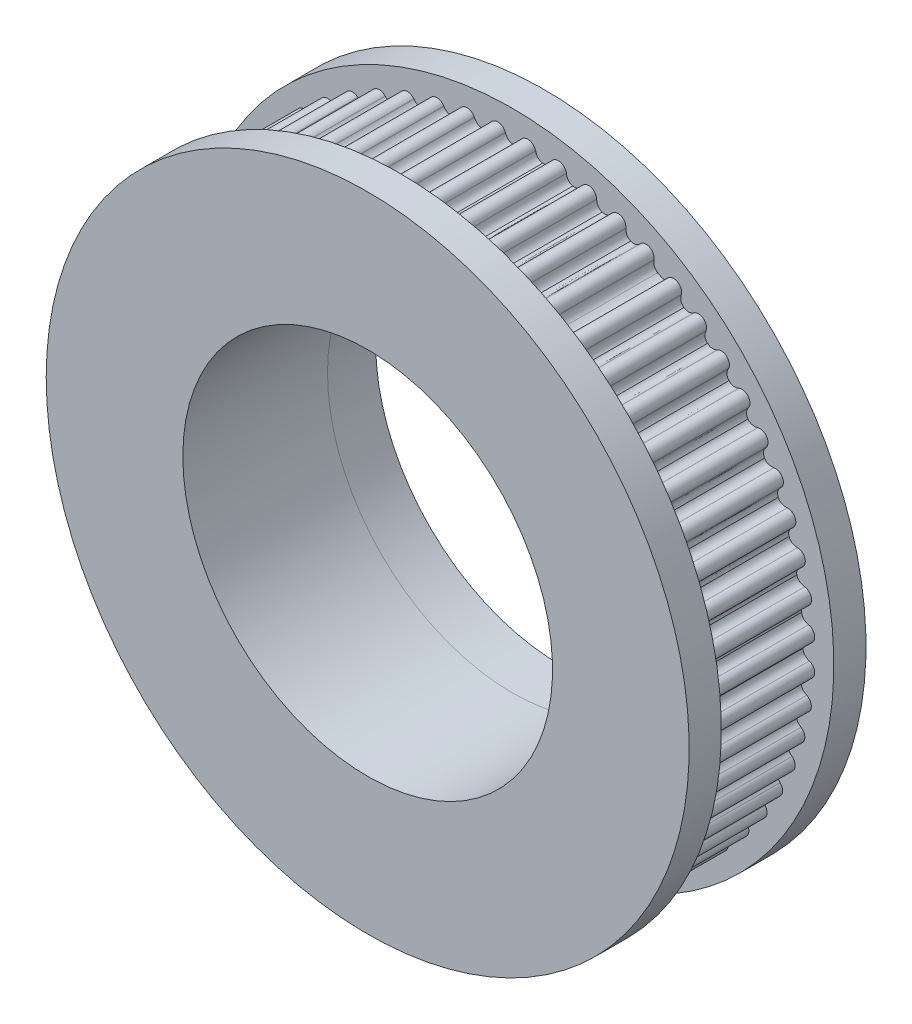
SolidWorks part; units mm, degrees
other "Camera1"
other "Camera2"
other "Camera3"
ref_plane "Front" through (0, 0, 0) normal (0, 0, 1) x (1, 0, 0)
ref_plane "Top" through (0, 0, 0) normal (0, 1, 0) x (1, 0, 0)
ref_plane "Right" through (0, 0, 0) normal (1, 0, 0) x (0, 0, -1)
sketch "Sketch1" plane through (0, 0, 0) normal (1, 0, 0) x (0, 0, -1)
  line L0 (0, 0) -> (-24.4032, 0) construction
  line L1 (0, 11.5) -> (0, 13.5)
  line L2 (0, 13.5) -> (-1, 13.5)
  line L3 (-1, 13.5) -> (-1, 18.85)
  line L4 (-3, 18.85) -> (-10, 18.85)
  line L5 (-12, 18.85) -> (-12, 11.5)
  line L6 (-12, 11.5) -> (0, 11.5)
  line L7 (-1, 18.85) -> (-1, 20)
  line L9 (-3, 20) -> (-3, 18.85)
  line L10 (-12, 13.3586) -> (-1, 13.3586) construction
  line L11 (-6.5, 18.85) -> (-6.5, 22.0506) construction
  line L12 (-10, 20) -> (-10, 18.85)
  line L14 (-12, 18.85) -> (-12, 20)
  line L15 (-12, 18.85) -> (-10, 18.85) construction
  line L16 (-3, 18.85) -> (-1, 18.85) construction
  line L17 (-12, 20) -> (-10, 20)
  line L18 (-3, 20) -> (-1, 20)
  circle A0 centre (-0.5, 11.5) radius 2 construction
  point P22 (-0.5, 13.5)
  point P24 (-6.5, 13.3586)
  dimension "D9" = 4
  dimension "D1" = 12
  dimension "D2" = 11
  dimension "D3" = 7
  dimension "D4" = 37.7
  dimension "D5" = 40
  dimension "D6" = 0
  dimension "D7" = 27
  dimension "D8" = 23
revolve "Revolve1" add sketch "Sketch1" angle 360 about L0
ref_plane "Plane2" through (0, 0, 3) normal (0, 0, 1) x (1, 0, 0)
ref_plane "Plane3" through (0, 0, 10) normal (0, 0, -1) x (-1, 0, 0)
sketch "Sketch3" plane through (0, 0, 3) normal (0, 0, 1) x (1, 0, 0)
  line L0 (0.4895, 18.4804) -> (0.4858, 18.4697)
  line L1 (-0.4323, 18.471) -> (-0.436, 18.4817)
  line L2 (-1.3914, 18.4344) -> (-1.394, 18.4234)
  line L3 (-2.3607, 18.3247) -> (-2.3654, 18.3349)
  line L4 (-3.3107, 18.188) -> (-3.3122, 18.1768)
  line L5 (-4.2632, 17.9775) -> (-4.269, 17.9872)
  line L6 (-5.1937, 17.7423) -> (-5.194, 17.731)
  line L7 (-6.119, 17.4334) -> (-6.1258, 17.4424)
  line L8 (-7.0199, 17.1022) -> (-7.019, 17.0909)
  line L9 (-7.9078, 16.6983) -> (-7.9155, 16.7066)
  line L10 (-8.7691, 16.2747) -> (-8.767, 16.2636)
  line L11 (-9.6099, 15.7803) -> (-9.6184, 15.7877)
  line L12 (-10.4222, 15.269) -> (-10.419, 15.2581)
  line L13 (-11.2067, 14.6893) -> (-11.216, 14.6958)
  line L14 (-11.9612, 14.0959) -> (-11.9568, 14.0855)
  line L15 (-12.6808, 13.4374) -> (-12.6907, 13.4429)
  line L16 (-13.3691, 12.7684) -> (-13.3637, 12.7585)
  line L17 (-14.0159, 12.0383) -> (-14.0263, 12.0427)
  line L18 (-14.6305, 11.301) -> (-14.6241, 11.2917)
  line L19 (-15.1975, 10.5073) -> (-15.2083, 10.5106)
  line L20 (-15.7316, 9.7098) -> (-15.7243, 9.7012)
  line L21 (-16.2125, 8.8612) -> (-16.2236, 8.8633)
  line L22 (-16.6604, 8.0122) -> (-16.6522, 8.0044)
  line L23 (-17.05, 7.118) -> (-17.0612, 7.1189)
  line L24 (-17.4066, 6.2268) -> (-17.3977, 6.22)
  line L25 (-17.7006, 5.2968) -> (-17.7119, 5.2965)
  line L26 (-17.9621, 4.3732) -> (-17.9525, 4.3673)
  line L27 (-18.1573, 3.4175) -> (-18.1685, 3.4161)
  line L28 (-18.3209, 2.4717) -> (-18.3107, 2.4669)
  line L29 (-18.415, 1.5008) -> (-18.426, 1.4983)
  line L30 (-18.4789, 0.5431) -> (-18.4682, 0.5394)
  line L31 (-18.471, -0.4323) -> (-18.4817, -0.436)
  line L32 (-18.4344, -1.3914) -> (-18.4234, -1.394)
  line L33 (-18.3247, -2.3607) -> (-18.3349, -2.3654)
  line L34 (-18.188, -3.3107) -> (-18.1768, -3.3122)
  line L35 (-17.9775, -4.2632) -> (-17.9872, -4.269)
  line L36 (-17.7423, -5.1937) -> (-17.731, -5.194)
  line L37 (-17.4334, -6.119) -> (-17.4424, -6.1258)
  line L38 (-17.1022, -7.0199) -> (-17.0909, -7.019)
  line L39 (-16.6983, -7.9078) -> (-16.7066, -7.9155)
  line L40 (-16.2747, -8.7691) -> (-16.2636, -8.767)
  line L41 (-15.7803, -9.6099) -> (-15.7877, -9.6184)
  line L42 (-15.269, -10.4222) -> (-15.2581, -10.419)
  line L43 (-14.6893, -11.2067) -> (-14.6958, -11.216)
  line L44 (-14.0959, -11.9612) -> (-14.0855, -11.9568)
  line L45 (-13.4374, -12.6808) -> (-13.4429, -12.6907)
  line L46 (-12.7684, -13.3691) -> (-12.7585, -13.3637)
  line L47 (-12.0383, -14.0159) -> (-12.0427, -14.0263)
  line L48 (-11.301, -14.6305) -> (-11.2917, -14.6241)
  line L49 (-10.5073, -15.1975) -> (-10.5106, -15.2083)
  line L50 (-9.7098, -15.7316) -> (-9.7012, -15.7243)
  line L51 (-8.8612, -16.2125) -> (-8.8633, -16.2236)
  line L52 (-8.0122, -16.6604) -> (-8.0044, -16.6522)
  line L53 (-7.118, -17.05) -> (-7.1189, -17.0612)
  line L54 (-6.2268, -17.4066) -> (-6.22, -17.3977)
  line L55 (-5.2968, -17.7006) -> (-5.2965, -17.7119)
  line L56 (-4.3732, -17.9621) -> (-4.3673, -17.9525)
  line L57 (-3.4175, -18.1573) -> (-3.4161, -18.1685)
  line L58 (-2.4717, -18.3209) -> (-2.4669, -18.3107)
  line L59 (-1.5008, -18.415) -> (-1.4983, -18.426)
  line L60 (-0.5431, -18.4789) -> (-0.5394, -18.4682)
  line L61 (0.4323, -18.471) -> (0.436, -18.4817)
  line L62 (1.3914, -18.4344) -> (1.394, -18.4234)
  line L63 (2.3607, -18.3247) -> (2.3654, -18.3349)
  line L64 (3.3107, -18.188) -> (3.3122, -18.1768)
  line L65 (4.2632, -17.9775) -> (4.269, -17.9872)
  line L66 (5.1937, -17.7423) -> (5.194, -17.731)
  line L67 (6.119, -17.4334) -> (6.1258, -17.4424)
  line L68 (7.0199, -17.1022) -> (7.019, -17.0909)
  line L69 (7.9078, -16.6983) -> (7.9155, -16.7066)
  line L70 (8.7691, -16.2747) -> (8.767, -16.2636)
  line L71 (9.6099, -15.7803) -> (9.6184, -15.7877)
  line L72 (10.4222, -15.269) -> (10.419, -15.2581)
  line L73 (11.2067, -14.6893) -> (11.216, -14.6958)
  line L74 (11.9612, -14.0959) -> (11.9568, -14.0855)
  line L75 (12.6808, -13.4374) -> (12.6907, -13.4429)
  line L76 (13.3691, -12.7684) -> (13.3637, -12.7585)
  line L77 (14.0159, -12.0383) -> (14.0263, -12.0427)
  line L78 (14.6305, -11.301) -> (14.6241, -11.2917)
  line L79 (15.1975, -10.5073) -> (15.2083, -10.5106)
  line L80 (15.7316, -9.7098) -> (15.7243, -9.7012)
  line L81 (16.2125, -8.8612) -> (16.2236, -8.8633)
  line L82 (16.6604, -8.0122) -> (16.6522, -8.0044)
  line L83 (17.05, -7.118) -> (17.0612, -7.1189)
  line L84 (17.4066, -6.2268) -> (17.3977, -6.22)
  line L85 (17.7006, -5.2968) -> (17.7119, -5.2965)
  line L86 (17.9621, -4.3732) -> (17.9525, -4.3673)
  line L87 (18.1573, -3.4175) -> (18.1685, -3.4161)
  line L88 (18.3209, -2.4717) -> (18.3107, -2.4669)
  line L89 (18.415, -1.5008) -> (18.426, -1.4983)
  line L90 (18.4789, -0.5431) -> (18.4682, -0.5394)
  line L91 (18.471, 0.4323) -> (18.4817, 0.436)
  line L92 (18.4344, 1.3914) -> (18.4234, 1.394)
  line L93 (18.3247, 2.3607) -> (18.3349, 2.3654)
  line L94 (18.188, 3.3107) -> (18.1768, 3.3122)
  line L95 (17.9775, 4.2632) -> (17.9872, 4.269)
  line L96 (17.7423, 5.1937) -> (17.731, 5.194)
  line L97 (17.4334, 6.119) -> (17.4424, 6.1258)
  line L98 (17.1022, 7.0199) -> (17.0909, 7.019)
  line L99 (16.6983, 7.9078) -> (16.7066, 7.9155)
  line L100 (16.2747, 8.7691) -> (16.2636, 8.767)
  line L101 (15.7803, 9.6099) -> (15.7877, 9.6184)
  line L102 (15.269, 10.4222) -> (15.2581, 10.419)
  line L103 (14.6893, 11.2067) -> (14.6958, 11.216)
  line L104 (14.0959, 11.9612) -> (14.0855, 11.9568)
  line L105 (13.4374, 12.6808) -> (13.4429, 12.6907)
  line L106 (12.7684, 13.3691) -> (12.7585, 13.3637)
  line L107 (12.0383, 14.0159) -> (12.0427, 14.0263)
  line L108 (11.301, 14.6305) -> (11.2917, 14.6241)
  line L109 (10.5073, 15.1975) -> (10.5106, 15.2083)
  line L110 (9.7098, 15.7316) -> (9.7012, 15.7243)
  line L111 (8.8141, 16.2382) -> (8.8162, 16.2492)
  line L112 (7.9639, 16.6835) -> (7.9561, 16.6753)
  line L113 (7.0685, 17.0705) -> (7.0694, 17.0818)
  line L114 (6.1763, 17.4246) -> (6.1695, 17.4156)
  line L115 (5.2454, 17.7159) -> (5.2452, 17.7272)
  line L116 (4.3211, 17.9748) -> (4.3153, 17.9651)
  line L117 (3.3649, 18.1671) -> (3.3634, 18.1783)
  line L118 (2.4186, 18.328) -> (2.4138, 18.3178)
  line L119 (1.4475, 18.4193) -> (1.4449, 18.4303)
  arc A0 (-0.436, 18.4817) -> (-1.3914, 18.4344) centre (-0.9065, 18.3126) ccw
  arc A1 (-2.3654, 18.3349) -> (-3.3107, 18.188) centre (-2.8157, 18.1175) ccw
  arc A2 (-4.269, 17.9872) -> (-5.1937, 17.7423) centre (-4.6941, 17.7239) ccw
  arc A3 (-6.1258, 17.4424) -> (-7.0199, 17.1022) centre (-6.521, 17.1362) ccw
  arc A4 (-7.9155, 16.7066) -> (-8.7691, 16.2747) centre (-8.2765, 16.3607) ccw
  arc A5 (-9.6184, 15.7877) -> (-10.4222, 15.269) centre (-9.9413, 15.4059) ccw
  arc A6 (-11.216, 14.6958) -> (-11.9612, 14.0959) centre (-11.4972, 14.2824) ccw
  arc A7 (-12.6907, 13.4429) -> (-13.3691, 12.7684) centre (-12.9272, 13.0023) ccw
  arc A8 (-14.0263, 12.0427) -> (-14.6305, 11.301) centre (-14.2155, 11.5798) ccw
  arc A9 (-15.2083, 10.5106) -> (-15.7316, 9.7098) centre (-15.348, 10.0305) ccw
  arc A10 (-16.2236, 8.8633) -> (-16.6604, 8.0122) centre (-16.3124, 8.3712) ccw
  arc A11 (-17.0612, 7.1189) -> (-17.4066, 6.2268) centre (-17.0981, 6.6203) ccw
  arc A12 (-17.7119, 5.2965) -> (-17.9621, 4.3732) centre (-17.6964, 4.7968) ccw
  arc A13 (-18.1685, 3.4161) -> (-18.3209, 2.4717) centre (-18.1009, 2.9207) ccw
  arc A14 (-18.426, 1.4983) -> (-18.4789, 0.5431) centre (-18.307, 1.0127) ccw
  arc A15 (-18.4817, -0.436) -> (-18.4344, -1.3914) centre (-18.3126, -0.9065) ccw
  arc A16 (-18.3349, -2.3654) -> (-18.188, -3.3107) centre (-18.1175, -2.8157) ccw
  arc A17 (-17.9872, -4.269) -> (-17.7423, -5.1937) centre (-17.7239, -4.6941) ccw
  arc A18 (-17.4424, -6.1258) -> (-17.1022, -7.0199) centre (-17.1362, -6.521) ccw
  arc A19 (-16.7066, -7.9155) -> (-16.2747, -8.7691) centre (-16.3607, -8.2765) ccw
  arc A20 (-15.7877, -9.6184) -> (-15.269, -10.4222) centre (-15.4059, -9.9413) ccw
  arc A21 (-14.6958, -11.216) -> (-14.0959, -11.9612) centre (-14.2824, -11.4972) ccw
  arc A22 (-13.4429, -12.6907) -> (-12.7684, -13.3691) centre (-13.0023, -12.9272) ccw
  arc A23 (-12.0427, -14.0263) -> (-11.301, -14.6305) centre (-11.5798, -14.2155) ccw
  arc A24 (-10.5106, -15.2083) -> (-9.7098, -15.7316) centre (-10.0305, -15.348) ccw
  arc A25 (-8.8633, -16.2236) -> (-8.0122, -16.6604) centre (-8.3712, -16.3124) ccw
  arc A26 (-7.1189, -17.0612) -> (-6.2268, -17.4066) centre (-6.6203, -17.0981) ccw
  arc A27 (-5.2965, -17.7119) -> (-4.3732, -17.9621) centre (-4.7968, -17.6964) ccw
  arc A28 (-3.4161, -18.1685) -> (-2.4717, -18.3209) centre (-2.9207, -18.1009) ccw
  arc A29 (-1.4983, -18.426) -> (-0.5431, -18.4789) centre (-1.0127, -18.307) ccw
  arc A30 (0.436, -18.4817) -> (1.3914, -18.4344) centre (0.9065, -18.3126) ccw
  arc A31 (2.3654, -18.3349) -> (3.3107, -18.188) centre (2.8157, -18.1175) ccw
  arc A32 (4.269, -17.9872) -> (5.1937, -17.7423) centre (4.6941, -17.7239) ccw
  arc A33 (6.1258, -17.4424) -> (7.0199, -17.1022) centre (6.521, -17.1362) ccw
  arc A34 (7.9155, -16.7066) -> (8.7691, -16.2747) centre (8.2765, -16.3607) ccw
  arc A35 (9.6184, -15.7877) -> (10.4222, -15.269) centre (9.9413, -15.4059) ccw
  arc A36 (11.216, -14.6958) -> (11.9612, -14.0959) centre (11.4972, -14.2824) ccw
  arc A37 (12.6907, -13.4429) -> (13.3691, -12.7684) centre (12.9272, -13.0023) ccw
  arc A38 (14.0263, -12.0427) -> (14.6305, -11.301) centre (14.2155, -11.5798) ccw
  arc A39 (15.2083, -10.5106) -> (15.7316, -9.7098) centre (15.348, -10.0305) ccw
  arc A40 (16.2236, -8.8633) -> (16.6604, -8.0122) centre (16.3124, -8.3712) ccw
  arc A41 (17.0612, -7.1189) -> (17.4066, -6.2268) centre (17.0981, -6.6203) ccw
  arc A42 (17.7119, -5.2965) -> (17.9621, -4.3732) centre (17.6964, -4.7968) ccw
  arc A43 (18.1685, -3.4161) -> (18.3209, -2.4717) centre (18.1009, -2.9207) ccw
  arc A44 (18.426, -1.4983) -> (18.4789, -0.5431) centre (18.307, -1.0127) ccw
  arc A45 (18.4817, 0.436) -> (18.4344, 1.3914) centre (18.3126, 0.9065) ccw
  arc A46 (18.3349, 2.3654) -> (18.188, 3.3107) centre (18.1175, 2.8157) ccw
  arc A47 (17.9872, 4.269) -> (17.7423, 5.1937) centre (17.7239, 4.6941) ccw
  arc A48 (17.4424, 6.1258) -> (17.1022, 7.0199) centre (17.1362, 6.521) ccw
  arc A49 (16.7066, 7.9155) -> (16.2747, 8.7691) centre (16.3607, 8.2765) ccw
  arc A50 (15.7877, 9.6184) -> (15.269, 10.4222) centre (15.4059, 9.9413) ccw
  arc A51 (14.6958, 11.216) -> (14.0959, 11.9612) centre (14.2824, 11.4972) ccw
  arc A52 (13.4429, 12.6907) -> (12.7684, 13.3691) centre (13.0023, 12.9272) ccw
  arc A53 (12.0427, 14.0263) -> (11.301, 14.6305) centre (11.5798, 14.2155) ccw
  arc A54 (10.5106, 15.2083) -> (9.7098, 15.7316) centre (10.0305, 15.348) ccw
  arc A55 (8.8162, 16.2492) -> (7.9639, 16.6835) centre (8.3239, 16.3366) ccw
  arc A56 (7.0694, 17.0818) -> (6.1763, 17.4246) centre (6.5707, 17.1172) ccw
  arc A57 (5.2452, 17.7272) -> (4.3211, 17.9748) centre (4.7454, 17.7103) ccw
  arc A58 (3.3634, 18.1783) -> (2.4186, 18.328) centre (2.8682, 18.1093) ccw
  arc A59 (1.4449, 18.4303) -> (0.4895, 18.4804) centre (0.9596, 18.3099) ccw
  spline S0 degree 3 poles (0.4858, 18.4697) (0.4077, 18.2495) (0.2403, 18.0862) (0.0262, 18.0851) knots 0 0 0 0 1 1 1 1
  spline S1 degree 3 poles (0.0262, 18.0851) (-0.1878, 18.0868) (-0.3548, 18.2506) (-0.4323, 18.471) knots 0 0 0 0 1 1 1 1
  spline S2 degree 3 poles (-1.394, 18.4234) (-1.4515, 18.1875) (-1.5982, 18.0156) (-1.8382, 17.9913) knots 0 0 0 0 1 1 1 1
  spline S3 degree 3 poles (-1.8382, 17.9913) (-2.0782, 17.9665) (-2.2567, 18.1053) (-2.3607, 18.3247) knots 0 0 0 0 1 1 1 1
  spline S4 degree 3 poles (-3.3122, 18.1768) (-3.3447, 17.9362) (-3.4726, 17.7498) (-3.7088, 17.7006) knots 0 0 0 0 1 1 1 1
  spline S5 degree 3 poles (-3.7088, 17.7006) (-3.9448, 17.6509) (-4.1368, 17.7702) (-4.2632, 17.9775) knots 0 0 0 0 1 1 1 1
  spline S6 degree 3 poles (-5.194, 17.731) (-5.2012, 17.4883) (-5.309, 17.2896) (-5.5387, 17.216) knots 0 0 0 0 1 1 1 1
  spline S7 degree 3 poles (-5.5387, 17.216) (-5.7682, 17.1418) (-5.9717, 17.2404) (-6.119, 17.4334) knots 0 0 0 0 1 1 1 1
  spline S8 degree 3 poles (-7.019, 17.0909) (-7.0007, 16.8488) (-7.0871, 16.6399) (-7.3079, 16.5427) knots 0 0 0 0 1 1 1 1
  spline S9 degree 3 poles (-7.3079, 16.5427) (-7.5284, 16.445) (-7.7411, 16.5218) (-7.9078, 16.6983) knots 0 0 0 0 1 1 1 1
  spline S10 degree 3 poles (-8.767, 16.2636) (-8.7236, 16.0248) (-8.7877, 15.808) (-8.9971, 15.6882) knots 0 0 0 0 1 1 1 1
  spline S11 degree 3 poles (-8.9971, 15.6882) (-9.2062, 15.568) (-9.4256, 15.6221) (-9.6099, 15.7803) knots 0 0 0 0 1 1 1 1
  spline S12 degree 3 poles (-10.419, 15.2581) (-10.3508, 15.0251) (-10.3919, 14.8028) (-10.5876, 14.6618) knots 0 0 0 0 1 1 1 1
  spline S13 degree 3 poles (-10.5876, 14.6618) (-10.783, 14.5204) (-11.007, 14.5513) (-11.2067, 14.6893) knots 0 0 0 0 1 1 1 1
  spline S14 degree 3 poles (-11.9568, 14.0855) (-11.8647, 13.8608) (-11.8823, 13.6355) (-12.0622, 13.4748) knots 0 0 0 0 1 1 1 1
  spline S15 degree 3 poles (-12.0622, 13.4748) (-12.2418, 13.3137) (-12.4677, 13.321) (-12.6808, 13.4374) knots 0 0 0 0 1 1 1 1
  spline S16 degree 3 poles (-13.3637, 12.7585) (-13.2485, 12.5447) (-13.2425, 12.3187) (-13.4046, 12.1401) knots 0 0 0 0 1 1 1 1
  spline S17 degree 3 poles (-13.4046, 12.1401) (-13.5664, 11.9611) (-13.7918, 11.9448) (-14.0159, 12.0383) knots 0 0 0 0 1 1 1 1
  spline S18 degree 3 poles (-14.6241, 11.2917) (-14.4872, 11.0912) (-14.4576, 10.867) (-14.6002, 10.6725) knots 0 0 0 0 1 1 1 1
  spline S19 degree 3 poles (-14.6002, 10.6725) (-14.7423, 10.4776) (-14.9648, 10.4378) (-15.1975, 10.5073) knots 0 0 0 0 1 1 1 1
  spline S20 degree 3 poles (-15.7243, 9.7012) (-15.5672, 9.5161) (-15.5143, 9.2963) (-15.6358, 9.0879) knots 0 0 0 0 1 1 1 1
  spline S21 degree 3 poles (-15.6358, 9.0879) (-15.7568, 8.8792) (-15.9739, 8.8163) (-16.2125, 8.8612) knots 0 0 0 0 1 1 1 1
  spline S22 degree 3 poles (-16.6522, 8.0044) (-16.4766, 7.8367) (-16.4011, 7.6237) (-16.5001, 7.4037) knots 0 0 0 0 1 1 1 1
  spline S23 degree 3 poles (-16.5001, 7.4037) (-16.5986, 7.1835) (-16.808, 7.0983) (-17.05, 7.118) knots 0 0 0 0 1 1 1 1
  spline S24 degree 3 poles (-17.3977, 6.22) (-17.2055, 6.0715) (-17.1081, 5.8675) (-17.1836, 5.6384) knots 0 0 0 0 1 1 1 1
  spline S25 degree 3 poles (-17.1836, 5.6384) (-17.2585, 5.4091) (-17.4579, 5.3025) (-17.7006, 5.2968) knots 0 0 0 0 1 1 1 1
  spline S26 degree 3 poles (-17.9525, 4.3673) (-17.7459, 4.2398) (-17.6277, 4.0471) (-17.6788, 3.8114) knots 0 0 0 0 1 1 1 1
  spline S27 degree 3 poles (-17.6788, 3.8114) (-17.7294, 3.5755) (-17.9165, 3.4486) (-18.1573, 3.4175) knots 0 0 0 0 1 1 1 1
  spline S28 degree 3 poles (-18.3107, 2.4669) (-18.0919, 2.3616) (-17.9542, 2.1823) (-17.9804, 1.9425) knots 0 0 0 0 1 1 1 1
  spline S29 degree 3 poles (-17.9804, 1.9425) (-18.006, 1.7027) (-18.1788, 1.5569) (-18.415, 1.5008) knots 0 0 0 0 1 1 1 1
  spline S30 degree 3 poles (-18.4682, 0.5394) (-18.2396, 0.4576) (-18.0839, 0.2937) (-18.0849, 0.0524) knots 0 0 0 0 1 1 1 1
  spline S31 degree 3 poles (-18.0849, 0.0524) (-18.0853, -0.1888) (-18.242, -0.3518) (-18.471, -0.4323) knots 0 0 0 0 1 1 1 1
  spline S32 degree 3 poles (-18.4234, -1.394) (-18.1875, -1.4515) (-18.0156, -1.5982) (-17.9913, -1.8382) knots 0 0 0 0 1 1 1 1
  spline S33 degree 3 poles (-17.9913, -1.8382) (-17.9665, -2.0782) (-18.1053, -2.2567) (-18.3247, -2.3607) knots 0 0 0 0 1 1 1 1
  spline S34 degree 3 poles (-18.1768, -3.3122) (-17.9362, -3.3447) (-17.7498, -3.4726) (-17.7006, -3.7088) knots 0 0 0 0 1 1 1 1
  spline S35 degree 3 poles (-17.7006, -3.7088) (-17.6509, -3.9448) (-17.7702, -4.1368) (-17.9775, -4.2632) knots 0 0 0 0 1 1 1 1
  spline S36 degree 3 poles (-17.731, -5.194) (-17.4883, -5.2012) (-17.2896, -5.309) (-17.216, -5.5387) knots 0 0 0 0 1 1 1 1
  spline S37 degree 3 poles (-17.216, -5.5387) (-17.1418, -5.7682) (-17.2404, -5.9717) (-17.4334, -6.119) knots 0 0 0 0 1 1 1 1
  spline S38 degree 3 poles (-17.0909, -7.019) (-16.8488, -7.0007) (-16.6399, -7.0871) (-16.5427, -7.3079) knots 0 0 0 0 1 1 1 1
  spline S39 degree 3 poles (-16.5427, -7.3079) (-16.445, -7.5284) (-16.5218, -7.7411) (-16.6983, -7.9078) knots 0 0 0 0 1 1 1 1
  spline S40 degree 3 poles (-16.2636, -8.767) (-16.0248, -8.7236) (-15.808, -8.7877) (-15.6882, -8.9971) knots 0 0 0 0 1 1 1 1
  spline S41 degree 3 poles (-15.6882, -8.9971) (-15.568, -9.2062) (-15.6221, -9.4256) (-15.7803, -9.6099) knots 0 0 0 0 1 1 1 1
  spline S42 degree 3 poles (-15.2581, -10.419) (-15.0251, -10.3508) (-14.8028, -10.3919) (-14.6618, -10.5876) knots 0 0 0 0 1 1 1 1
  spline S43 degree 3 poles (-14.6618, -10.5876) (-14.5204, -10.783) (-14.5513, -11.007) (-14.6893, -11.2067) knots 0 0 0 0 1 1 1 1
  spline S44 degree 3 poles (-14.0855, -11.9568) (-13.8608, -11.8647) (-13.6355, -11.8823) (-13.4748, -12.0622) knots 0 0 0 0 1 1 1 1
  spline S45 degree 3 poles (-13.4748, -12.0622) (-13.3137, -12.2418) (-13.321, -12.4677) (-13.4374, -12.6808) knots 0 0 0 0 1 1 1 1
  spline S46 degree 3 poles (-12.7585, -13.3637) (-12.5447, -13.2485) (-12.3187, -13.2425) (-12.1401, -13.4046) knots 0 0 0 0 1 1 1 1
  spline S47 degree 3 poles (-12.1401, -13.4046) (-11.9611, -13.5664) (-11.9448, -13.7918) (-12.0383, -14.0159) knots 0 0 0 0 1 1 1 1
  spline S48 degree 3 poles (-11.2917, -14.6241) (-11.0912, -14.4872) (-10.867, -14.4576) (-10.6725, -14.6002) knots 0 0 0 0 1 1 1 1
  spline S49 degree 3 poles (-10.6725, -14.6002) (-10.4776, -14.7423) (-10.4378, -14.9648) (-10.5073, -15.1975) knots 0 0 0 0 1 1 1 1
  spline S50 degree 3 poles (-9.7012, -15.7243) (-9.5161, -15.5672) (-9.2963, -15.5143) (-9.0879, -15.6358) knots 0 0 0 0 1 1 1 1
  spline S51 degree 3 poles (-9.0879, -15.6358) (-8.8792, -15.7568) (-8.8163, -15.9739) (-8.8612, -16.2125) knots 0 0 0 0 1 1 1 1
  spline S52 degree 3 poles (-8.0044, -16.6522) (-7.8367, -16.4766) (-7.6237, -16.4011) (-7.4037, -16.5001) knots 0 0 0 0 1 1 1 1
  spline S53 degree 3 poles (-7.4037, -16.5001) (-7.1835, -16.5986) (-7.0983, -16.808) (-7.118, -17.05) knots 0 0 0 0 1 1 1 1
  spline S54 degree 3 poles (-6.22, -17.3977) (-6.0715, -17.2055) (-5.8675, -17.1081) (-5.6384, -17.1836) knots 0 0 0 0 1 1 1 1
  spline S55 degree 3 poles (-5.6384, -17.1836) (-5.4091, -17.2585) (-5.3025, -17.4579) (-5.2968, -17.7006) knots 0 0 0 0 1 1 1 1
  spline S56 degree 3 poles (-4.3673, -17.9525) (-4.2398, -17.7459) (-4.0471, -17.6277) (-3.8114, -17.6788) knots 0 0 0 0 1 1 1 1
  spline S57 degree 3 poles (-3.8114, -17.6788) (-3.5755, -17.7294) (-3.4486, -17.9165) (-3.4175, -18.1573) knots 0 0 0 0 1 1 1 1
  spline S58 degree 3 poles (-2.4669, -18.3107) (-2.3616, -18.0919) (-2.1823, -17.9542) (-1.9425, -17.9804) knots 0 0 0 0 1 1 1 1
  spline S59 degree 3 poles (-1.9425, -17.9804) (-1.7027, -18.006) (-1.5569, -18.1788) (-1.5008, -18.415) knots 0 0 0 0 1 1 1 1
  spline S60 degree 3 poles (-0.5394, -18.4682) (-0.4576, -18.2396) (-0.2937, -18.0839) (-0.0524, -18.0849) knots 0 0 0 0 1 1 1 1
  spline S61 degree 3 poles (-0.0524, -18.0849) (0.1888, -18.0853) (0.3518, -18.242) (0.4323, -18.471) knots 0 0 0 0 1 1 1 1
  spline S62 degree 3 poles (1.394, -18.4234) (1.4515, -18.1875) (1.5982, -18.0156) (1.8382, -17.9913) knots 0 0 0 0 1 1 1 1
  spline S63 degree 3 poles (1.8382, -17.9913) (2.0782, -17.9665) (2.2567, -18.1053) (2.3607, -18.3247) knots 0 0 0 0 1 1 1 1
  spline S64 degree 3 poles (3.3122, -18.1768) (3.3447, -17.9362) (3.4726, -17.7498) (3.7088, -17.7006) knots 0 0 0 0 1 1 1 1
  spline S65 degree 3 poles (3.7088, -17.7006) (3.9448, -17.6509) (4.1368, -17.7702) (4.2632, -17.9775) knots 0 0 0 0 1 1 1 1
  spline S66 degree 3 poles (5.194, -17.731) (5.2012, -17.4883) (5.309, -17.2896) (5.5387, -17.216) knots 0 0 0 0 1 1 1 1
  spline S67 degree 3 poles (5.5387, -17.216) (5.7682, -17.1418) (5.9717, -17.2404) (6.119, -17.4334) knots 0 0 0 0 1 1 1 1
  spline S68 degree 3 poles (7.019, -17.0909) (7.0007, -16.8488) (7.0871, -16.6399) (7.3079, -16.5427) knots 0 0 0 0 1 1 1 1
  spline S69 degree 3 poles (7.3079, -16.5427) (7.5284, -16.445) (7.7411, -16.5218) (7.9078, -16.6983) knots 0 0 0 0 1 1 1 1
  spline S70 degree 3 poles (8.767, -16.2636) (8.7236, -16.0248) (8.7877, -15.808) (8.9971, -15.6882) knots 0 0 0 0 1 1 1 1
  spline S71 degree 3 poles (8.9971, -15.6882) (9.2062, -15.568) (9.4256, -15.6221) (9.6099, -15.7803) knots 0 0 0 0 1 1 1 1
  spline S72 degree 3 poles (10.419, -15.2581) (10.3508, -15.0251) (10.3919, -14.8028) (10.5876, -14.6618) knots 0 0 0 0 1 1 1 1
  spline S73 degree 3 poles (10.5876, -14.6618) (10.783, -14.5204) (11.007, -14.5513) (11.2067, -14.6893) knots 0 0 0 0 1 1 1 1
  spline S74 degree 3 poles (11.9568, -14.0855) (11.8647, -13.8608) (11.8823, -13.6355) (12.0622, -13.4748) knots 0 0 0 0 1 1 1 1
  spline S75 degree 3 poles (12.0622, -13.4748) (12.2418, -13.3137) (12.4677, -13.321) (12.6808, -13.4374) knots 0 0 0 0 1 1 1 1
  spline S76 degree 3 poles (13.3637, -12.7585) (13.2485, -12.5447) (13.2425, -12.3187) (13.4046, -12.1401) knots 0 0 0 0 1 1 1 1
  spline S77 degree 3 poles (13.4046, -12.1401) (13.5664, -11.9611) (13.7918, -11.9448) (14.0159, -12.0383) knots 0 0 0 0 1 1 1 1
  spline S78 degree 3 poles (14.6241, -11.2917) (14.4872, -11.0912) (14.4576, -10.867) (14.6002, -10.6725) knots 0 0 0 0 1 1 1 1
  spline S79 degree 3 poles (14.6002, -10.6725) (14.7423, -10.4776) (14.9648, -10.4378) (15.1975, -10.5073) knots 0 0 0 0 1 1 1 1
  spline S80 degree 3 poles (15.7243, -9.7012) (15.5672, -9.5161) (15.5143, -9.2963) (15.6358, -9.0879) knots 0 0 0 0 1 1 1 1
  spline S81 degree 3 poles (15.6358, -9.0879) (15.7568, -8.8792) (15.9739, -8.8163) (16.2125, -8.8612) knots 0 0 0 0 1 1 1 1
  spline S82 degree 3 poles (16.6522, -8.0044) (16.4766, -7.8367) (16.4011, -7.6237) (16.5001, -7.4037) knots 0 0 0 0 1 1 1 1
  spline S83 degree 3 poles (16.5001, -7.4037) (16.5986, -7.1835) (16.808, -7.0983) (17.05, -7.118) knots 0 0 0 0 1 1 1 1
  spline S84 degree 3 poles (17.3977, -6.22) (17.2055, -6.0715) (17.1081, -5.8675) (17.1836, -5.6384) knots 0 0 0 0 1 1 1 1
  spline S85 degree 3 poles (17.1836, -5.6384) (17.2585, -5.4091) (17.4579, -5.3025) (17.7006, -5.2968) knots 0 0 0 0 1 1 1 1
  spline S86 degree 3 poles (17.9525, -4.3673) (17.7459, -4.2398) (17.6277, -4.0471) (17.6788, -3.8114) knots 0 0 0 0 1 1 1 1
  spline S87 degree 3 poles (17.6788, -3.8114) (17.7294, -3.5755) (17.9165, -3.4486) (18.1573, -3.4175) knots 0 0 0 0 1 1 1 1
  spline S88 degree 3 poles (18.3107, -2.4669) (18.0919, -2.3616) (17.9542, -2.1823) (17.9804, -1.9425) knots 0 0 0 0 1 1 1 1
  spline S89 degree 3 poles (17.9804, -1.9425) (18.006, -1.7027) (18.1788, -1.5569) (18.415, -1.5008) knots 0 0 0 0 1 1 1 1
  spline S90 degree 3 poles (18.4682, -0.5394) (18.2396, -0.4576) (18.0839, -0.2937) (18.0849, -0.0524) knots 0 0 0 0 1 1 1 1
  spline S91 degree 3 poles (18.0849, -0.0524) (18.0853, 0.1888) (18.242, 0.3518) (18.471, 0.4323) knots 0 0 0 0 1 1 1 1
  spline S92 degree 3 poles (18.4234, 1.394) (18.1875, 1.4515) (18.0156, 1.5982) (17.9913, 1.8382) knots 0 0 0 0 1 1 1 1
  spline S93 degree 3 poles (17.9913, 1.8382) (17.9665, 2.0782) (18.1053, 2.2567) (18.3247, 2.3607) knots 0 0 0 0 1 1 1 1
  spline S94 degree 3 poles (18.1768, 3.3122) (17.9362, 3.3447) (17.7498, 3.4726) (17.7006, 3.7088) knots 0 0 0 0 1 1 1 1
  spline S95 degree 3 poles (17.7006, 3.7088) (17.6509, 3.9448) (17.7702, 4.1368) (17.9775, 4.2632) knots 0 0 0 0 1 1 1 1
  spline S96 degree 3 poles (17.731, 5.194) (17.4883, 5.2012) (17.2896, 5.309) (17.216, 5.5387) knots 0 0 0 0 1 1 1 1
  spline S97 degree 3 poles (17.216, 5.5387) (17.1418, 5.7682) (17.2404, 5.9717) (17.4334, 6.119) knots 0 0 0 0 1 1 1 1
  spline S98 degree 3 poles (17.0909, 7.019) (16.8488, 7.0007) (16.6399, 7.0871) (16.5427, 7.3079) knots 0 0 0 0 1 1 1 1
  spline S99 degree 3 poles (16.5427, 7.3079) (16.445, 7.5284) (16.5218, 7.7411) (16.6983, 7.9078) knots 0 0 0 0 1 1 1 1
  spline S100 degree 3 poles (16.2636, 8.767) (16.0248, 8.7236) (15.808, 8.7877) (15.6882, 8.9971) knots 0 0 0 0 1 1 1 1
  spline S101 degree 3 poles (15.6882, 8.9971) (15.568, 9.2062) (15.6221, 9.4256) (15.7803, 9.6099) knots 0 0 0 0 1 1 1 1
  spline S102 degree 3 poles (15.2581, 10.419) (15.0251, 10.3508) (14.8028, 10.3919) (14.6618, 10.5876) knots 0 0 0 0 1 1 1 1
  spline S103 degree 3 poles (14.6618, 10.5876) (14.5204, 10.783) (14.5513, 11.007) (14.6893, 11.2067) knots 0 0 0 0 1 1 1 1
  spline S104 degree 3 poles (14.0855, 11.9568) (13.8608, 11.8647) (13.6355, 11.8823) (13.4748, 12.0622) knots 0 0 0 0 1 1 1 1
  spline S105 degree 3 poles (13.4748, 12.0622) (13.3137, 12.2418) (13.321, 12.4677) (13.4374, 12.6808) knots 0 0 0 0 1 1 1 1
  spline S106 degree 3 poles (12.7585, 13.3637) (12.5447, 13.2485) (12.3187, 13.2425) (12.1401, 13.4046) knots 0 0 0 0 1 1 1 1
  spline S107 degree 3 poles (12.1401, 13.4046) (11.9611, 13.5664) (11.9448, 13.7918) (12.0383, 14.0159) knots 0 0 0 0 1 1 1 1
  spline S108 degree 3 poles (11.2917, 14.6241) (11.0912, 14.4872) (10.867, 14.4576) (10.6725, 14.6002) knots 0 0 0 0 1 1 1 1
  spline S109 degree 3 poles (10.6725, 14.6002) (10.4776, 14.7423) (10.4378, 14.9648) (10.5073, 15.1975) knots 0 0 0 0 1 1 1 1
  spline S110 degree 3 poles (9.7012, 15.7243) (9.5161, 15.5672) (9.5993, 15.3388) (9.0425, 15.6621) knots 0 0 0 0 1 1 1 1
  spline S111 degree 3 poles (9.0425, 15.6621) (8.8334, 15.7824) (8.77, 15.9994) (8.8141, 16.2382) knots 0 0 0 0 1 1 1 1
  spline S112 degree 3 poles (7.9561, 16.6753) (7.7889, 16.4993) (7.5761, 16.4231) (7.3558, 16.5215) knots 0 0 0 0 1 1 1 1
  spline S113 degree 3 poles (7.3558, 16.5215) (7.1353, 16.6193) (7.0495, 16.8285) (7.0685, 17.0705) knots 0 0 0 0 1 1 1 1
  spline S114 degree 3 poles (6.1695, 17.4156) (6.0216, 17.2231) (5.8179, 17.125) (5.5886, 17.1999) knots 0 0 0 0 1 1 1 1
  spline S115 degree 3 poles (5.5886, 17.1999) (5.3591, 17.2741) (5.2519, 17.4732) (5.2454, 17.7159) knots 0 0 0 0 1 1 1 1
  spline S116 degree 3 poles (4.3153, 17.9651) (4.1883, 17.7581) (3.996, 17.6394) (3.7601, 17.6898) knots 0 0 0 0 1 1 1 1
  spline S117 degree 3 poles (3.7601, 17.6898) (3.5241, 17.7397) (3.3967, 17.9264) (3.3649, 18.1671) knots 0 0 0 0 1 1 1 1
  spline S118 degree 3 poles (2.4138, 18.3178) (2.3091, 18.0986) (2.1303, 17.9604) (1.8904, 17.9859) knots 0 0 0 0 1 1 1 1
  spline S119 degree 3 poles (1.8904, 17.9859) (1.6505, 18.0109) (1.5042, 18.1832) (1.4475, 18.4193) knots 0 0 0 0 1 1 1 1
extrude "Cut-Extrude1" cut sketch "Sketch3" along normal up to surface (7 mm away) flip side to cut up to plane "Plane3"
sketch "Sketch4" plane through (0, 0, 0) normal (1, 0, 0) x (0, 0, -1)
  line L0 (-3, 21.4747) -> (-3, -21.2713)
split "Split1" trim tools "Sketch4" bodies to split 103 resulting bodies 107 108
